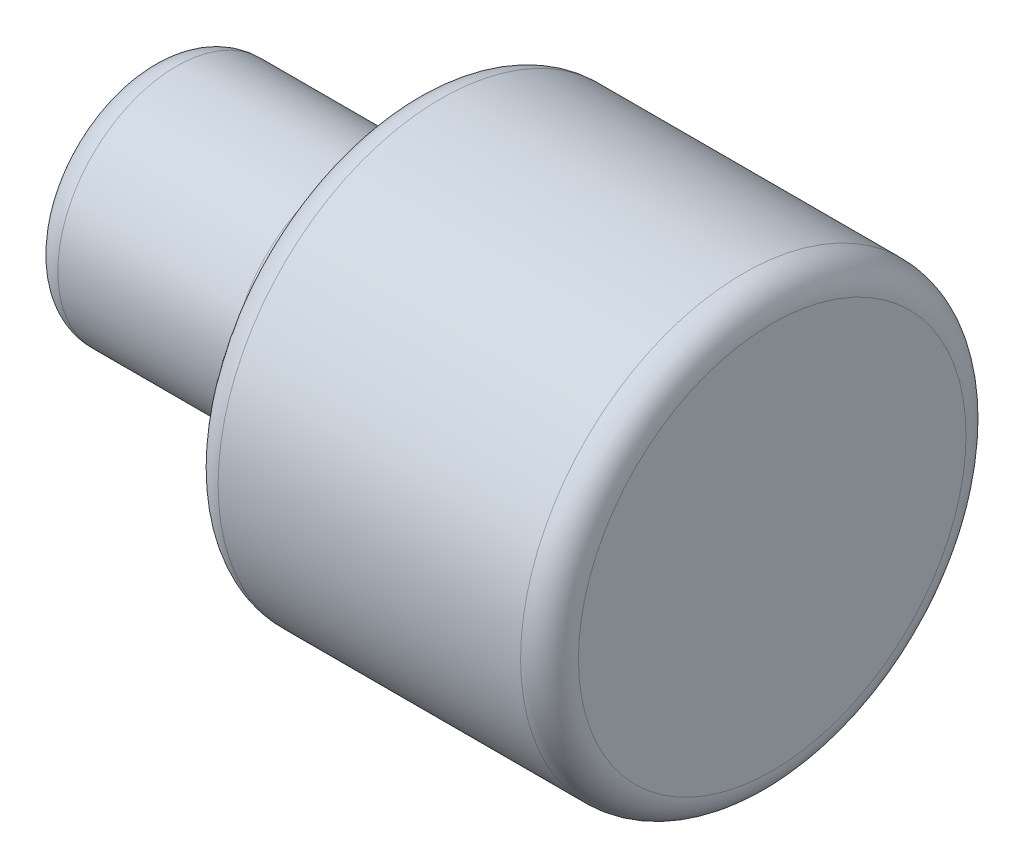
SolidWorks part; units mm, degrees
ref_plane "Alzado" through (0, 0, 0) normal (1, 0, 0) x (0, 1, 0)
ref_plane "Planta" through (0, 0, 0) normal (0, 0, 1) x (0, 1, 0)
ref_plane "Vista lateral" through (0, 0, 0) normal (0, 1, 0) x (-1, 0, 0)
sketch "Croquis1" plane through (0, 0, 0) normal (1, 0, 0) x (0, 1, 0)
  circle A0 centre (0, 0) radius 3.85
  circle A1 centre (0, 0) radius 2.05
  dimension "D1" = 7.7
  dimension "D2" = 4.1
extrude "Saliente-Extruir1" add sketch "Croquis1" along normal blind 6 contours A0 A1 | A1 region at (0, -3.7411, 0) region at (0, 0, 0)
extrude "Saliente-Extruir2" add sketch "Croquis1<3>" against normal blind 4.8 contours A1 region at (0, 0, 0)
sketch "Croquis1<3>" plane through (0, 0, 0) normal (1, 0, 0) x (0, 1, 0) same geometry as "Croquis1"
chamfer "Chaflán1" distance 1 distance2 1.85 1 edges at (0, 0, -2.05) first distance on face at (-4.8, 0, -2.05)
fillet "Redondeo1" radius 0.5 4 edges at (-0.027, 0, -3.85) (6, 0, -3.85) (-4.8, 0, -2.05) (-1, 0, -2.05)
